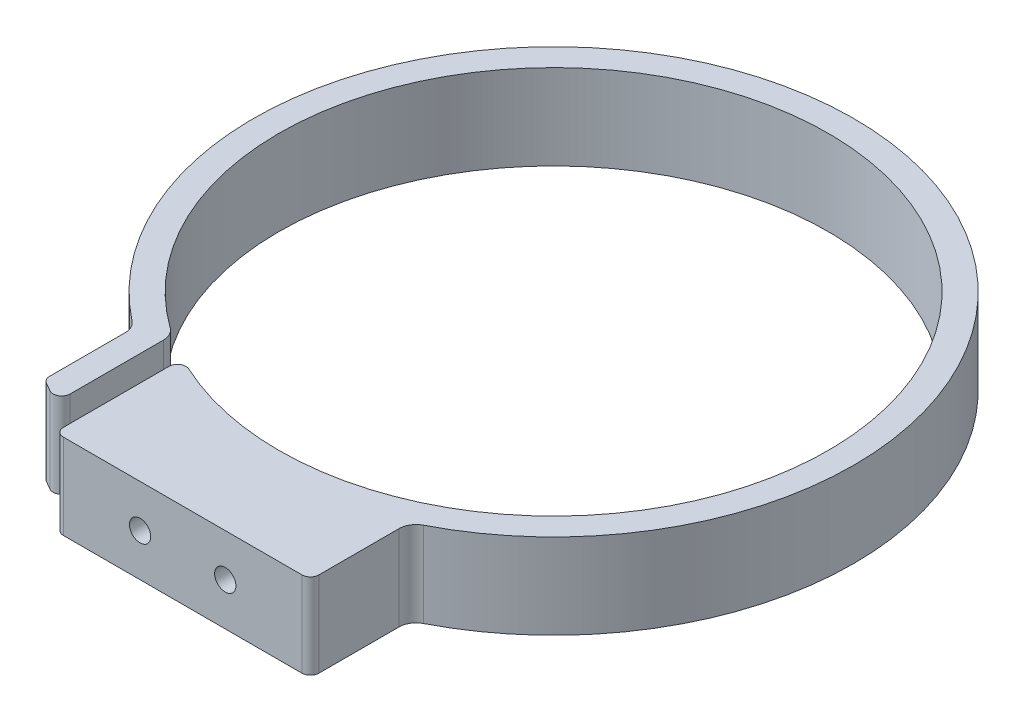
SolidWorks part; units mm, degrees
material "Сплав 2024"
ref_plane "Спереди" through (0, 0, 0) normal (0, 0, 1) x (1, 0, 0)
ref_plane "Сверху" through (0, 0, 0) normal (0, 1, 0) x (1, 0, 0)
ref_plane "Справа" through (0, 0, 0) normal (1, 0, 0) x (0, 0, -1)
sketch "Эскиз1" plane through (0, 0, 0) normal (0, 1, 0) x (1, 0, 0)
  line L0 (-15, -28.5493) -> (-15, -43.5493) construction
  line L1 (-15, -43.5493) -> (15, -43.5493) construction
  line L2 (15, -43.5493) -> (15, -28.5493) construction
  line L3 (15, -28.5493) -> (-15, -28.5493) construction
  line L4 (-15, -31.8993) -> (-15, -43.5493)
  line L5 (-15, -43.5493) -> (15, -43.5493)
  line L6 (15, -43.5493) -> (15, -31.8993)
  circle A0 centre (0, 0) radius 32.25
  arc A1 (15, -31.8993) -> (-15, -31.8993) centre (0, 0) ccw
  circle A3 centre (0, 0) radius 35.25 construction
  point P7 (-15, -31.8993)
  point P10 (15, -31.8993)
  point P12 (35.25, 0)
  dimension "D1" = 64.5
  dimension "D3" = 30
  dimension "D4" = 15
  dimension "D2" = 3
extrude "Бобышка-Вытянуть1" add sketch "Эскиз1" along normal blind 10
ref_plane "Плоскость1" through (15, 0, 0) normal (1, 0, 0) x (0, 0, -1)
ref_plane "Плоскость2" through (-15, 0, 0) normal (1, 0, 0) x (0, 0, -1)
sketch "Эскиз4" plane through (0, 10, 0) normal (0, 1, 0) x (1, 0, 0)
  line L1 (-15, -31.8993) -> (-18, -31.8993)
  line L2 (-15, -31.8993) -> (-15, -23.7125)
  line L3 (-15, -23.7125) -> (-18, -23.7125)
  line L4 (-18, -31.8993) -> (-18, -23.7125)
  dimension "D1" = 3
  dimension "D2" = 8.1867
extrude "Вырез-Вытянуть2" cut sketch "Эскиз4" against normal up to surface (10 mm away) up to face at (0, 0, 20.937)
sketch "Эскиз11" plane through (0, 10, 0) normal (0, 1, 0) x (1, 0, 0)
  line L1 (-18, -26.7593) -> (-21, -26.7593)
  line L2 (-18, -26.7593) -> (-18, -40.4914)
  line L3 (-18, -40.4914) -> (-21, -38.7593)
  line L4 (-21, -26.7593) -> (-21, -38.7593)
  dimension "D1" = 3
  dimension "D2" = 120
  dimension "D3" = 12
extrude "Бобышка-Вытянуть5" add sketch "Эскиз11" against normal up to surface (10 mm away) up to face at (0.037, 0, 13.8254)
sketch "Эскиз12" plane through (-21, 0, 0) normal (-1, 0, 0) x (0, 0, 1)
  line L0 (38.7593, 5) -> (28.3119, 5) construction
  line L1 (38.7593, 0) -> (38.7593, 10) construction
  line L2 (28.3119, 0) -> (28.3119, 10) construction
  line L3 (33.7593, 10) -> (33.7593, 0) construction
  dimension "D1" = 5
hole_wizard "Отверстие с зазором M32" positions "Эскиз14" profile "Эскиз13" hole size "M3" standard "Ansi Metric" end condition up to next
sketch "Эскиз14" plane through (-21, 0, 0) normal (-1, 0, 0) x (0, 0, 1)
  line L1 (33.7593, 10) -> (33.7593, 0) construction
  point P0 (33.7593, 5)
sketch "Эскиз13" plane through (-21, 5, 33.7593) normal (0, 1, 0) x (0, 0, 1)
  line L0 (0, 0) -> (0, 3)
  line L1 (0, 3) -> (1.7, 3)
  line L2 (1.7, 3) -> (1.7, 0)
  line L5 (1.7, 0) -> (0, 0)
  line L11 (0, -6.35) -> (0, 107.95) construction
  dimension "Диаметр сквозного отверстия" = 3.4
  dimension "Глубина сквозного отверстия" = 3
hole_wizard "Отверстие обработанное метчиком M3x0.51" positions "Эскиз16" profile "Эскиз15" tap size "M3x0.5" standard "Ansi Metric"
sketch "Эскиз16" plane through (-15, 0, 0) normal (-1, 0, 0) x (0, 0, 1)
  line L1 (33.7593, 10) -> (33.7593, 0) construction
  line L2 (38.7593, 5) -> (28.3119, 5) construction
  point P0 (33.7593, 5)
sketch "Эскиз15" plane through (-15, 5, 33.7593) normal (0, 1, 0) x (0, 0, 1)
  line L0 (0, 0) -> (0, 9.2511)
  line L1 (0, 9.2511) -> (1.25, 8.5)
  line L2 (1.25, 8.5) -> (1.25, 0)
  line L5 (1.25, 0) -> (0, 0)
  line L10 (0, 9.2511) -> (-1.25, 8.5) construction
  line L11 (0, -6.35) -> (0, 107.95) construction
  dimension "Диаметр сверла" = 2.5
  dimension "Глубина сверла" = 8.5
  dimension "Угол заточки сверла" = 118
cosmetic thread "Отверстие резьбы1" parameters "D1"=6, "D2"=3
sketch "Эскиз17" plane through (0, 0, 43.5493) normal (0, 0, 1) x (1, 0, 0)
  line L0 (-15, 5) -> (15, 5) construction
  line L1 (-15, 10) -> (-15, 0) construction
  line L2 (15, 10) -> (15, 0) construction
  line L3 (-5, 10) -> (-5, 0) construction
  line L4 (-15, 10) -> (15, 10) construction
  line L5 (-15, 0) -> (15, 0) construction
  line L6 (5, 10) -> (5, 0) construction
  line L7 (-15, 10) -> (-15, 0) construction
  dimension "D1" = 10
  dimension "D2" = 30
  dimension "D3" = 10
hole_wizard "Отверстие обработанное метчиком M3x0.52" positions "Эскиз19" profile "Эскиз18" tap size "M3x0.5" standard "Ansi Metric"
sketch "Эскиз19" plane through (0, 0, 43.5493) normal (0, 0, 1) x (1, 0, 0)
  line L0 (-5, 10) -> (-5, 0) construction
  line L1 (5, 10) -> (5, 0) construction
  point P0 (-5, 5)
  point P4 (5, 5)
sketch "Эскиз18" plane through (-5, 5, 43.5493) normal (1, 0, 0) x (0, -1, 0)
  line L0 (0, 0) -> (0, 9.2511)
  line L1 (0, 9.2511) -> (1.25, 8.5)
  line L2 (1.25, 8.5) -> (1.25, 0)
  line L5 (1.25, 0) -> (0, 0)
  line L10 (0, 9.2511) -> (-1.25, 8.5) construction
  line L11 (0, -6.35) -> (0, 107.95) construction
  dimension "Диаметр сверла" = 2.5
  dimension "Глубина сверла" = 8.5
  dimension "Угол заточки сверла" = 118
cosmetic thread "Отверстие резьбы2" parameters "D1"=6, "D2"=3
cosmetic thread "Отверстие резьбы3" parameters "D1"=6, "D2"=3
fillet "Скругление1" radius 2 3 edges at (15, 5, 31.8993) (-18, 5, 26.7593) (-21, 5, 28.3119)
fillet "Скругление2" radius 1 5 edges at (-15, 5, 28.5493) (-18, 5, 40.4914) (-21, 5, 38.7593) (15, 5, 43.5493) (-15, 5, 43.5493)
equation "\"D1@Эскиз17\"=\"D2@Эскиз17\"/3"
equation "\"D3@Эскиз17\"=\"D1@Эскиз17\""
